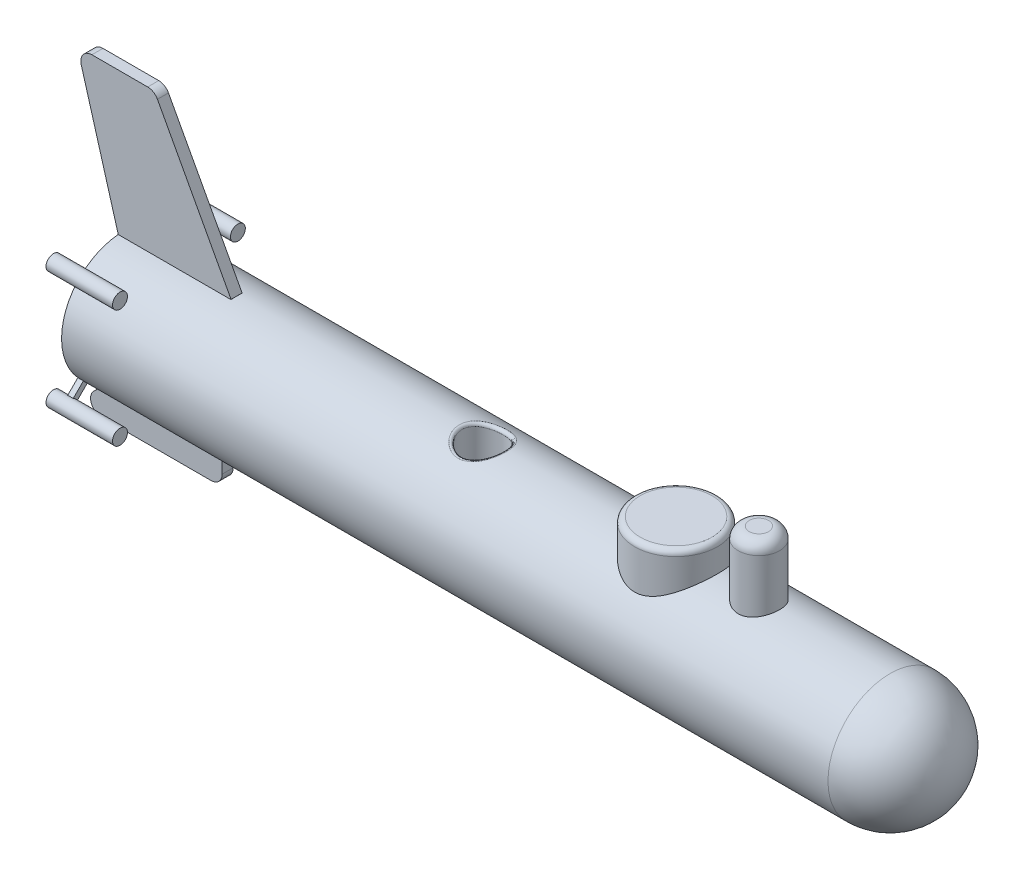
SolidWorks part; units mm, degrees
material "Вода"
ref_plane "Спереди" through (0, 0, 0) normal (0, 0, 1) x (1, 0, 0)
ref_plane "Сверху" through (0, 0, 0) normal (0, 1, 0) x (1, 0, 0)
ref_plane "Справа" through (0, 0, 0) normal (1, 0, 0) x (0, 0, -1)
sketch "Эскиз1" plane through (0, 0, 0) normal (1, 0, 0) x (0, 0, -1)
  circle A0 centre (0, 0) radius 225
  dimension "D1" = 450
extrude "Бобышка-Вытянуть1" add sketch "Эскиз1" along normal mid plane 3000
fillet "Скругление1" radius 225 1 edges at (1500, 0, -225)
sketch "Эскиз3" plane through (0, 0, 0) normal (0, 1, 0) x (1, 0, 0)
  line L0 (-1500, 225) -> (-1500, -225) construction
  line L1 (-1500, 225) -> (-1500, -225)
  line L2 (-1500, 0) -> (1500, 0) construction
  arc A0 (1275, -225) -> (1275, 225) centre (1275, 0) ccw construction
  circle A1 centre (500, 0) radius 150
  circle A2 centre (800, 0) radius 75
  circle A3 centre (-200, 0) radius 75
  dimension "D1" = 300
  dimension "D3" = 150
  dimension "D5" = 150
  dimension "D2" = 1000
  dimension "D4" = 700
  dimension "D6" = 200
extrude "Бобышка-Вытянуть2" add sketch "Эскиз3" along normal blind 330 contours L2 A1 | A1 L2 region at (500, 0, -63.662) region at (500, 0, 63.662)
fillet "Скругление2" radius 20 1 edges at (500, 330, 150)
extrude "Бобышка-Вытянуть3" add sketch "Эскиз3<3>" along normal blind 450 contours L2 A2 | A2 L2 region at (800, 0, -31.831) region at (800, 0, 31.831)
sketch "Эскиз3<3>" plane through (0, 0, 0) normal (0, 1, 0) x (1, 0, 0) same geometry as "Эскиз3"
fillet "Скругление3" radius 40 1 edges at (800, 450, 75)
sketch "Эскиз4" plane through (0, 0, 0) normal (0, 0, 1) x (1, 0, 0)
  line L0 (-1500, 225) -> (-1648.3648, 740.1672)
  line L1 (-1648.3648, 740.1672) -> (-1369.2401, 740.1672)
  line L2 (-1369.2401, 740.1672) -> (-1091.3001, 225)
  line L3 (350, 225) -> (-1500, 225) construction
  line L4 (-1123.6157, -225) -> (-1123.6157, -379.3221)
  line L5 (-1500, -225) -> (1275, -225) construction
  line L6 (-1123.6157, -379.3221) -> (-1658.312, -379.3221)
  line L7 (-1658.312, -379.3221) -> (-1500, -225)
  line L8 (350, 225) -> (-1500, 225)
  line L9 (-1500, -225) -> (1275, -225)
  line L11 (-1500, 225) -> (-1091.3001, 225)
  line L12 (-1500, 225) -> (-1500, 182.6501)
  line L13 (-1500, 182.6501) -> (-1091.3001, 182.6501)
  line L14 (-1091.3001, 225) -> (-1091.3001, 182.6501)
  line L15 (-1123.6157, -225) -> (-1500, -225)
  line L16 (-1123.6157, -225) -> (-1123.6157, -172.9951)
  line L17 (-1123.6157, -172.9951) -> (-1500, -172.9951)
  line L18 (-1500, -225) -> (-1500, -172.9951)
extrude "Бобышка-Вытянуть4" add sketch "Эскиз4" along normal mid plane 40 contours L8 L2 L1 L0 | L9 L7 L6 L4 | L14 L8 L12 L13 | L18 L9 L16 L17 region at (-1395.5338, 466.4087, 0) region at (-1295.6501, 203.8251, 0) region at (-1353.6782, -306.6303, 0) region at (-1311.8078, -198.9976, 0)
extrude "Вырез-Вытянуть1" cut sketch "Эскиз3<4>" against normal through all both and the other way through all contours L2 A3 | A3 L2 region at (-200, 0, -31.831) region at (-200, 0, 31.831)
sketch "Эскиз3<4>" plane through (0, 0, 0) normal (0, 1, 0) x (1, 0, 0) same geometry as "Эскиз3"
fillet "Скругление4" radius 40 4 edges at (-1648.3648, 740.1672, 0) (-1369.2401, 740.1672, 0) (-1123.6157, -379.3221, 0) (-1658.312, -379.3221, 0)
fillet "Скругление5" radius 10 2 edges at (-212.817, -212.5189, -73.8967) (-187.183, 212.5189, -73.8967)
sketch "Эскиз5" plane through (-1500, 0, 0) normal (-1, 0, 0) x (0, 0, 1)
  line L0 (0, 0) -> (-213.389, 213.389) construction
  line L1 (0, 0) -> (0, 225) construction
  line L2 (20, 225) -> (-20, 225) construction
  line L3 (-151.8707, 166.0129) -> (-188.5838, 202.726)
  line L4 (-166.0129, 151.8707) -> (-202.726, 188.5838)
  line L5 (-166.0129, 151.8707) -> (-151.8707, 166.0129)
  arc A2 (-20, 224.1093) -> (-20, -224.1093) centre (0, 0) ccw construction
  arc A3 (-20, 224.1093) -> (-20, -224.1093) centre (0, 0) ccw
  circle A4 centre (-213.389, 213.389) radius 27
  point P1 (-158.9418, 158.9418)
  arc M5 (-20, 224.1093) -> (-20, -224.1093) centre (0, 0) ccw
  dimension "D2" = 77
  dimension "D3" = 20
  dimension "D4" = 54
  dimension "D1" = 45
extrude "Бобышка-Вытянуть5" add sketch "Эскиз5" against normal blind 20 contours A4 L4 L3 M5 region at (-1500, 176.8971, -176.8971)
extrude "Бобышка-Вытянуть6" add sketch "Эскиз5<3>" along normal blind 41 and the other way blind 200 contours A4 region at (-1500, 213.389, -213.389)
sketch "Эскиз5<3>" plane through (-1500, 0, 0) normal (-1, 0, 0) x (0, 0, 1) same geometry as "Эскиз5"
pattern_circular "Круговой массив1" count 4 every 90 about axis through (1500, 0, 0) along (-1, 0, 0) of "Бобышка-Вытянуть5", "Бобышка-Вытянуть6"
